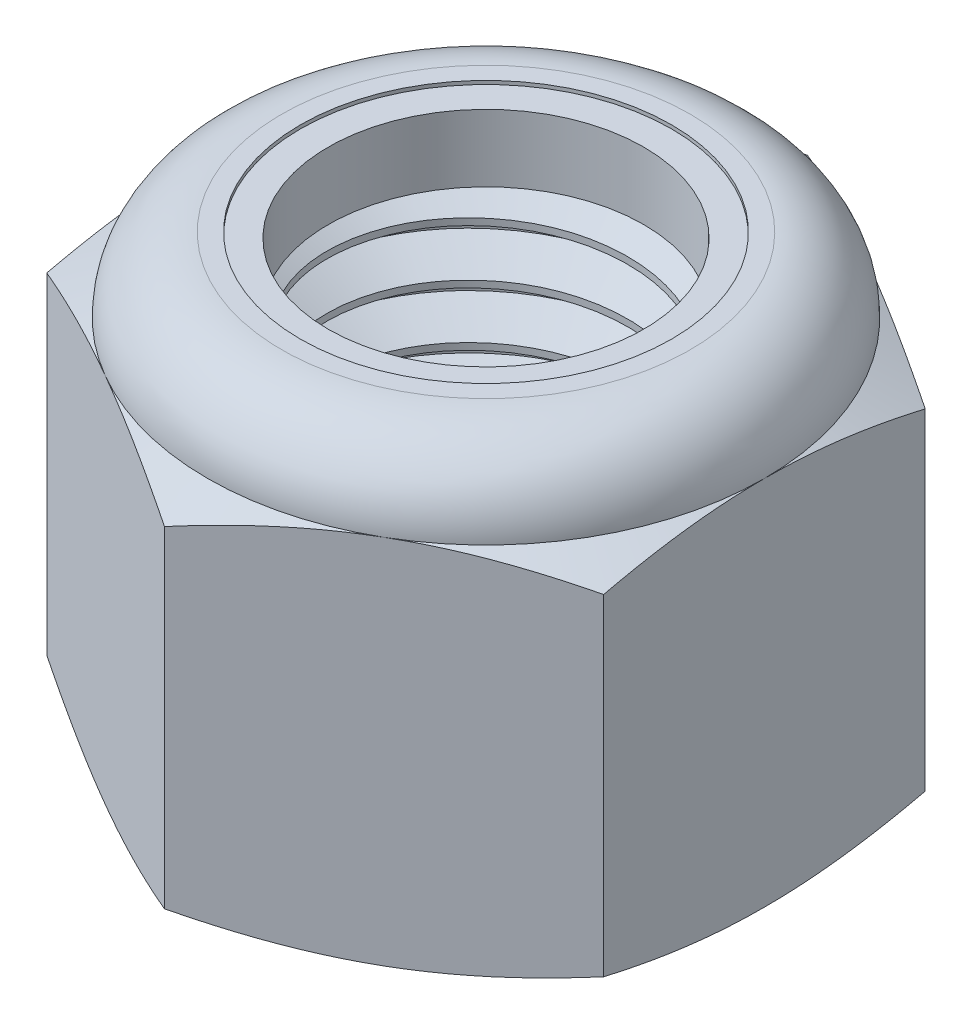
SolidWorks part; units mm, degrees
note: '?' marks a value the reader was unsure of.
ref_plane "Front" through (0, 0, 0) normal (0, 0, 1) x (1, 0, 0)
ref_plane "Top" through (0, 0, 0) normal (0, 1, 0) x (1, 0, 0)
ref_plane "Right" through (0, 0, 0) normal (1, 0, 0) x (0, 0, -1)
sketch "Sketch8" plane through (0, 0, 0) normal (1, 0, 0) x (0, 0, -1)
  line L0 (0, 0) -> (0, 19.05) construction
  line L1 (11.9062, 0) -> (-11.9062, 0) construction
  line L2 (-7.9375, 19.05) -> (7.9375, 19.05) construction
  line L3 (7.9375, 19.05) -> (7.9375, 16.7409) construction
sketch "Sketch1" plane through (0, 0, 0) normal (0, 1, 0) x (1, 0, 0)
  line L1 (0, 13.7482) -> (-11.9062, 6.8741)
  line L2 (-11.9062, 6.8741) -> (-11.9062, -6.8741)
  line L3 (-11.9062, -6.8741) -> (0, -13.7482)
  line L4 (0, -13.7482) -> (11.9063, -6.8741)
  line L5 (11.9063, -6.8741) -> (11.9063, 6.8741)
  line L6 (11.9063, 6.8741) -> (0, 13.7482)
  circle A0 centre (0, 0) radius 11.9062 construction
  circle A1 centre (0, 0) radius 7.9375
extrude "Extrude1" add sketch "Sketch1" along normal up to vertex (19.05 mm away) up to point (0, 19.05, 0)
sketch "Sketch5" plane through (0, 0, 0) normal (1, 0, 0) x (0, 0, -1)
  line L0 (0, 0) -> (11.9062, 0)
  line L1 (11.9062, 0) -> (13.7482, 0.8589)
  line L2 (13.7482, 0.8589) -> (13.7482, 15.0161)
  line L3 (13.7482, 15.0161) -> (11.9062, 15.875)
  line L4 (8.7312, 19.05) -> (8.7312, 20.32)
  line L5 (8.7312, 20.32) -> (15.0182, 20.32)
  line L6 (15.0182, 20.32) -> (15.0182, -1.27)
  line L7 (15.0182, -1.27) -> (0, -1.27)
  line L8 (0, -1.27) -> (0, 0)
  line L9 (11.9062, 15.875) -> (11.9062, 0) construction
  line L12 (13.7482, 19.05) -> (13.7482, 0) construction
  line L13 (13.7482, 9.525) -> (15.0182, 9.525) construction
  line L15 (0, 0) -> (0, 20.32) construction
  line L18 (11.9062, 0) -> (-11.9062, 0) construction
  line L19 (6.8741, 19.05) -> (13.7482, 19.05) construction
  line L20 (0, 20.32) -> (8.7312, 20.32) construction
  line L21 (6.8741, 0) -> (13.7482, 0) construction
  arc A0 (11.9062, 15.875) -> (8.7312, 19.05) centre (8.7312, 15.875) ccw
  dimension "D1" = 25
  dimension "D2" = 1.27
  dimension "D4" = 3.175
revolve "Cut-Revolve3" cut sketch "Sketch5" angle 360 about L15
sketch "Sketch4" plane through (0, 0, 0) normal (1, 0, 0) x (0, 0, -1)
  line L0 (0, 15.875) -> (8.7312, 15.875)
  line L1 (8.7312, 15.875) -> (0, 11.8036)
  line L3 (0, 4.0714) -> (8.7312, 0)
  line L4 (8.7312, 0) -> (0, 0)
  line L5 (0, 0) -> (0, 15.875) construction
  line L10 (0, 0) -> (0, 19.05) construction
  line L11 (0, 4.0714) -> (0, 0)
  line L12 (0, 15.875) -> (0, 11.8036)
  line L13 (10.3111, 15.875) -> (0, 15.875) construction
  dimension "D1" = 25
  dimension "D2" = 17.4625
sketch "Sketch6" plane through (0, 0, 0) normal (1, 0, 0) x (0, 0, -1)
  line L0 (0, 15.875) -> (11.7538, 15.875)
  line L1 (8.7312, 18.8976) -> (4.3656, 18.8976)
  line L2 (0, 20.32) -> (0, 15.875)
  line L3 (4.3656, 20.32) -> (0, 20.32)
  line L4 (0, 20.32) -> (8.7312, 20.32) construction
  line L5 (0, 0) -> (0, 20.32) construction
  line L6 (0, 20.32) -> (0, 0) construction
  line L7 (4.3656, 18.8976) -> (4.3656, 20.32)
  line L8 (8.7312, 19.05) -> (8.7312, 18.8976) construction
  line L9 (4.3656, 18.8976) -> (0, 18.8976) construction
  line L10 (0, 18.8976) -> (0, 11.8036) construction
  arc A0 (11.7538, 15.875) -> (8.7312, 18.8976) centre (8.7312, 15.875) ccw
  arc A1 (11.9062, 15.875) -> (8.7312, 19.05) centre (8.7312, 15.875) ccw construction
  dimension "D1" = 0.1524
revolve "Cut-Revolve4" cut sketch "Sketch6" angle 360 about L6
revolve "Cut-Revolve2" cut sketch "Sketch4" angle 360 about L5
sketch "Sketch7" plane through (0, 0, 0) normal (1, 0, 0) x (0, 0, -1)
  line L0 (6.7469, 15.9512) -> (11.6767, 15.9512)
  line L1 (8.7312, 18.8214) -> (6.7469, 18.8214)
  line L2 (6.7469, 18.8214) -> (6.7469, 15.9512)
  line L3 (6.7469, 15.9512) -> (0, 15.9512) construction
  line L4 (0, 15.9512) -> (0, 18.8214) construction
  line L5 (0, 18.8214) -> (6.7469, 18.8214) construction
  line L6 (6.7469, 15.9512) -> (6.7469, 15.875) construction
  line L7 (0, 15.875) -> (11.7538, 15.875) construction
  line L8 (8.7312, 18.8214) -> (8.7312, 18.8976) construction
  arc A0 (11.6767, 15.9512) -> (8.7312, 18.8214) centre (8.7312, 15.875) ccw
  arc A2 (11.7538, 15.875) -> (8.7312, 18.8976) centre (8.7312, 15.875) ccw construction
  dimension "D1" = 0.0762
  dimension "D2" = 13.4937
revolve "Revolve2" add sketch "Sketch7" angle 360 about L4
sketch "Sketch2" plane through (0, 0, 0) normal (1, 0, 0) x (0, 0, -1)
  line L0 (-7.9375, 0) -> (-7.9375, 15.875) construction
  line L1 (0, 0) -> (7.9375, 0)
  line L2 (0, 0) -> (0, 15.875)
  line L3 (0, 15.875) -> (7.9375, 15.875)
  line L4 (7.9375, 0) -> (7.9375, 15.875)
  line L6 (10.3111, 15.875) -> (11.9062, 15.875) construction
  line L7 (0, -7.9375) -> (0, 0) construction
revolve "Revolve1" add sketch "Sketch2" angle 360 about L7
sketch "Sketch9" plane through (0, 0, 0) normal (1, 0, 0) x (0, 0, -1)
  line L0 (8.1875, 18.0398) -> (8.1875, 15.7307) construction
  line L1 (8.1875, 15.7307) -> (6.1877, 16.8852) construction
  line L2 (6.1877, 16.8852) -> (8.1875, 18.0398) construction
  line L3 (6.4377, 17.0295) -> (6.4377, 16.7409) construction
  line L4 (7.9375, 17.8955) -> (7.9375, 15.875) construction
  line L5 (6.1877, 16.8852) -> (6.4377, 16.8852) construction
  line L6 (7.9375, 16.8852) -> (8.1875, 16.8852) construction
  line L7 (8.0625, 16.8852) -> (8.0625, 17.9676) construction
  line L8 (8.1875, 15.7307) -> (8.0625, 17.9676)
  line L9 (8.0625, 17.9676) -> (6.4377, 17.0295)
  line L10 (6.4377, 17.0295) -> (6.4377, 16.7409)
  line L11 (6.4377, 16.7409) -> (8.1875, 15.7307)
  dimension "D1" = 2.3091
  dimension "D2" = 0.2886
sketch "Sketch10" plane through (0, 15.875, 0) normal (0, 1, 0) x (1, 0, 0)
  circle A1 centre (0, 0) radius 7.9375
  circle A2 centre (0, 0) radius 7.9375
  dimension "D1" = 0
curve "Helix/Spiral1" pitch 2.3091 height 21.3591 turns 9.25
sweep "Cut-Sweep1" cut profiles "Sketch9" path "Helix/Spiral1" align with end faces yes
sketch "Sketch11" plane through (0, 0, 0) normal (1, 0, 0) x (0, 0, -1)
  line L0 (0, 0) -> (0, 19.05) construction
  line L1 (11.9062, 0) -> (-11.9062, 0) construction
  line L4 (0, 19.05) -> (0, 0) construction
  line L5 (0, 9.525) -> (7.9375, 9.525) construction
  line L6 (0, 0) -> (8.7312, 0)
  line L7 (0, 4.0714) -> (0, 0)
  line L8 (8.7312, 0) -> (0, 4.0714)
  dimension "D1" = 17.4625
  dimension "D2" = 25
revolve "Revolve3" add sketch "Sketch11" angle 360 about L4
sketch "Sketch12" plane through (0, 0, 0) normal (1, 0, 0) x (0, 0, -1)
  line L0 (8.7312, 15.875) -> (0, 15.875)
  line L1 (0, 15.875) -> (0, 0)
  line L2 (0, 0) -> (8.7312, 0)
  line L3 (11.9062, 0) -> (-11.9062, 0) construction
  line L4 (8.7312, 0) -> (8.7312, 15.875)
  line L5 (-8.7312, 0) -> (8.7312, 0) construction
revolve "Revolve4" add sketch "Sketch12" angle 360 about L0
combine bodies "Combine1" operation type subtract main body 136 bodies to subtract 133
ref_plane "Contact Plane 1" through (0, 0, 0) normal (0, -1, 0) x (1, 0, 0)
ref_axis "Center Axis 1" through (0, -2.1015, 0) along (0, 1, 0)?
equation "\"D4@Sketch5\"=\"Height@Sketch8\"/6"
equation "\"D1@Sketch9\"=\"Thread Pitch@Sketch8\""
equation "\"D2@Sketch9\"=\"Thread Pitch@Sketch8\"/8"
equation "\"D4@Helix/Spiral1\"=\"Thread Pitch@Sketch8\""
equation "\"D3@Helix/Spiral1\"=\"Thread Pitch@Sketch8\"+\"Height@Sketch8\""
equation "\"D2@Sketch4\"=\"Thread Dia@Sketch8\"*1.1"
equation "\"D1@Sketch11\"=\"Thread Dia@Sketch8\"*1.1"
equation "\"D2@Sketch7\"=\"Thread Dia@Sketch8\"*.85"
